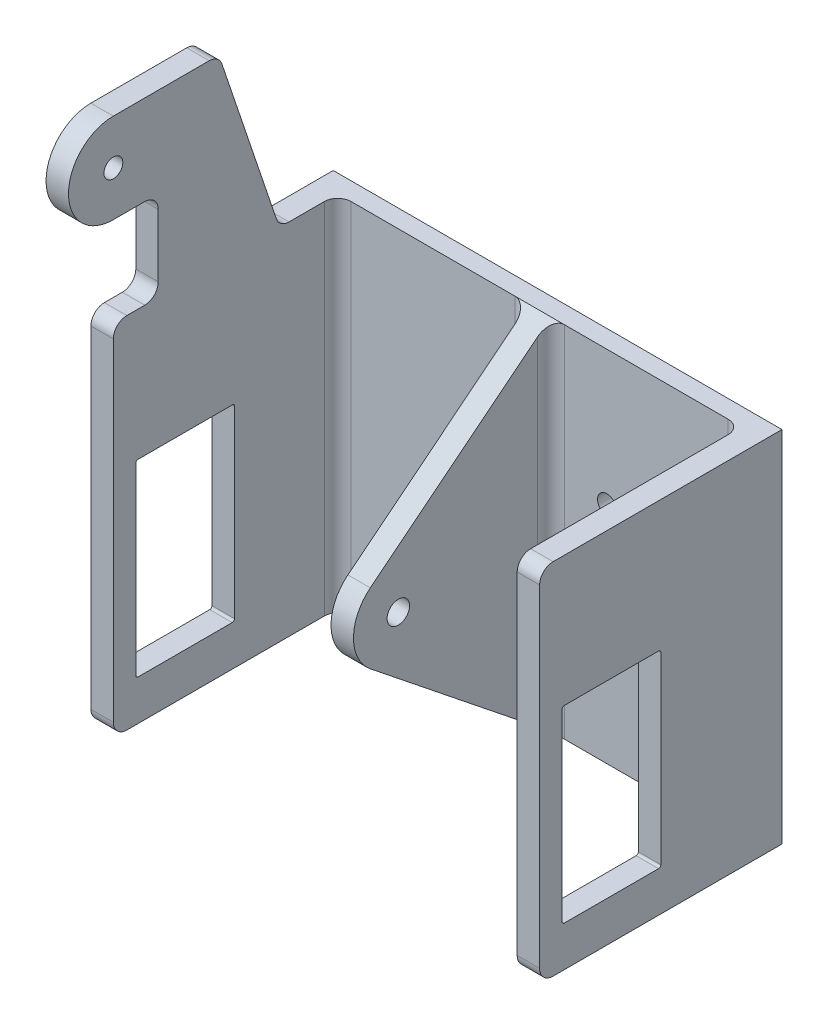
SolidWorks part; units mm, degrees
ref_plane "前视基准面" through (0, 0, 0) normal (0, 0, 1) x (1, 0, 0)
ref_plane "上视基准面" through (0, 0, 0) normal (0, 1, 0) x (1, 0, 0)
ref_plane "右视基准面" through (0, 0, 0) normal (1, 0, 0) x (0, 0, -1)
other "Configuration Table"
sketch "草图1" plane through (0, 0, 0) normal (0, 0, 1) x (1, 0, 0)
  line L1 (0, 0) -> (100, 0)
  line L2 (0, 0) -> (0, 80)
  line L3 (0, 80) -> (100, 80)
  line L4 (100, 0) -> (100, 80)
  dimension "D1" = 100
  dimension "D2" = 80
extrude "凸台-拉伸1" add sketch "草图1" along normal blind 4
sketch "草图2" plane through (0, 0, 4) normal (0, 0, 1) x (1, 0, 0)
  line L0 (0, 0) -> (100, 0) construction
  line L1 (0, 80) -> (5, 80)
  line L2 (0, 80) -> (0, 0)
  line L3 (0, 0) -> (5, 0)
  line L4 (5, 80) -> (5, 0)
  line L5 (100, 80) -> (0, 80) construction
  line L6 (100, 80) -> (95, 80)
  line L7 (100, 80) -> (100, 0)
  line L8 (100, 0) -> (95, 0)
  line L9 (95, 80) -> (95, 0)
  line L10 (47.5, 80) -> (52.5, 80)
  line L11 (47.5, 80) -> (47.5, 0)
  line L12 (47.5, 0) -> (52.5, 0)
  line L13 (52.5, 80) -> (52.5, 0)
  line L14 (50, 80) -> (50, 0) construction
  dimension "D1" = 5
  dimension "D2" = 5
  dimension "D3" = 5
  dimension "D4" = 50
extrude "凸台-拉伸2" add sketch "草图2" along normal blind 50
sketch "草图4" plane through (47.5, 0, 0) normal (-1, 0, 0) x (0, 0, 1)
  line L2 (4, 80) -> (54, 40)
  line L3 (54, 80) -> (54, 0) construction
  line L4 (54, 40) -> (4, 0)
  line L5 (54, 80) -> (4, 80) construction
  line L6 (54, 80) -> (4, 80)
  line L8 (54, 80) -> (54, 40)
  line L9 (54, 0) -> (4, 0) construction
  line L10 (54, 0) -> (4, 0)
  line L11 (54, 40) -> (54, 0)
  line M5 (4, 0) -> (54, 0)
  line M6 (54, 0) -> (54, 80)
  line M7 (54, 80) -> (4, 80)
extrude "切除-拉伸2" cut sketch "草图4" against normal blind 5 contours L2 M7 M6 | L4 M6 M5 region at (47.5, 66.6667, 37.3333) region at (47.5, 13.3333, 37.3333)
fillet "圆角1" radius 10 1 edges at (50, 40, 54)
fillet "圆角2" radius 3 6 edges at (97.5, 0, 54) (97.5, 80, 54) (2.5, 80, 54) (2.5, 0, 54) (95, 40, 4) (5, 40, 4)
fillet "圆角3" radius 3 2 edges at (47.5, 40, 4) (52.5, 40, 4)
sketch "草图5" plane through (0, 0, 0) normal (0, 0, -1) x (-1, 0, 0)
  line L0 (-50, 80) -> (-50, 0) construction
  line L1 (-100, 80) -> (0, 80) construction
  line L2 (0, 0) -> (-100, 0) construction
  line L3 (-100, 40) -> (0, 40) construction
  line L4 (-100, 0) -> (-100, 80) construction
  line L5 (0, 80) -> (0, 0) construction
  circle A0 centre (-65, 50) radius 2.1
  circle A1 centre (-35, 50) radius 2.1
  circle A2 centre (-65, 30) radius 2.1
  circle A3 centre (-35, 30) radius 2.1
  dimension "D1" = 4.2
  dimension "D3" = 20
  dimension "D2" = 30
extrude "切除-拉伸3" cut sketch "草图5" against normal blind 5
sketch "草图6" plane through (47.5, 0, 0) normal (-1, 0, 0) x (0, 0, 1)
  circle A0 centre (37.9922, 40) radius 2.5
  arc A3 (44.2391, 32.1913) -> (44.2391, 47.8087) centre (37.9922, 40) ccw construction
  dimension "D2" = 5
extrude "切除-拉伸4" cut sketch "草图6" against normal blind 10
sketch "草图7" plane through (0, 0, 0) normal (-1, 0, 0) x (0, 0, 1)
  line L0 (54, 77) -> (54, 3) construction
  line L1 (27, 51) -> (49, 51)
  line L2 (27, 51) -> (27, 9)
  line L3 (27, 9) -> (49, 9)
  line L4 (49, 51) -> (49, 9)
  line L5 (51, 0) -> (0, 0) construction
  dimension "D1" = 42
  dimension "D2" = 22
  dimension "D3" = 5
  dimension "D4" = 9
extrude "切除-拉伸5" cut sketch "草图7" against normal blind 10
sketch "草图8" plane through (100, 0, 0) normal (1, 0, 0) x (0, 0, -1)
  line L0 (-54, 3) -> (-54, 77) construction
  line L1 (-49, 9) -> (-27, 9)
  line L2 (-49, 9) -> (-49, 51)
  line L3 (-49, 51) -> (-27, 51)
  line L4 (-27, 9) -> (-27, 51)
  line L5 (-51, 0) -> (0, 0) construction
  dimension "D1" = 42
  dimension "D2" = 22
  dimension "D3" = 5
  dimension "D4" = 9
extrude "切除-拉伸6" cut sketch "草图8" against normal blind 10
fillet "圆角4" radius 0.5 4 edges at (97.5, 51, 27) (97.5, 51, 49) (97.5, 9, 49) (97.5, 9, 27)
fillet "圆角5" radius 0.5 4 edges at (2.5, 51, 49) (2.5, 9, 49) (2.5, 51, 27) (2.5, 9, 27)
sketch "草图9" plane through (0, 80, 0) normal (0, 1, 0) x (1, 0, 0)
  line L0 (0, -51) -> (0, 0) construction
  line L1 (0, -17) -> (5, -17)
  line L2 (0, -17) -> (0, -44)
  line L3 (0, -44) -> (5, -44)
  line L4 (5, -17) -> (5, -44)
  line L5 (5, -51) -> (5, -7) construction
  line L6 (5, -54) -> (0, -54) construction
  dimension "D1" = 10
  dimension "D2" = 27
extrude "凸台-拉伸3" add sketch "草图9" along normal blind 40
sketch "草图10" plane through (0, 0, 0) normal (-1, 0, 0) x (0, 0, 1)
  line L0 (17, 80) -> (30.5, 120)
  line L1 (17, 120) -> (44, 120) construction
  line L2 (30.5, 120) -> (17, 120)
  line L3 (17, 120) -> (17, 80)
extrude "切除-拉伸7" cut sketch "草图10" against normal blind 20
sketch "草图11" plane through (0, 0, 44) normal (0, 0, 1) x (1, 0, 0)
  line L0 (5, 120) -> (5, 80) construction
  line L1 (0, 120) -> (5, 120)
  line L2 (0, 120) -> (0, 100)
  line L3 (0, 100) -> (5, 100)
  line L4 (5, 120) -> (5, 100)
  dimension "D1" = 20
extrude "凸台-拉伸4" add sketch "草图11" along normal blind 20
fillet "圆角6" 2 edges at (2.5, 120, 64) (2.5, 100, 64) type full round first side face at (2.5, 120, 47.25) second side face at (2.5, 100, 54) middle face at (2.5, 110, 64)
fillet "圆角7" radius 3 4 edges at (2.5, 80, 44) (2.5, 100, 44) (2.5, 120, 30.5) (2.5, 80, 17)
sketch "草图12" plane through (0, 0, 0) normal (-1, 0, 0) x (0, 0, 1)
  circle A0 centre (54, 110) radius 2.1
  dimension "D1" = 4.2
extrude "切除-拉伸8" cut sketch "草图12" against normal blind 20
